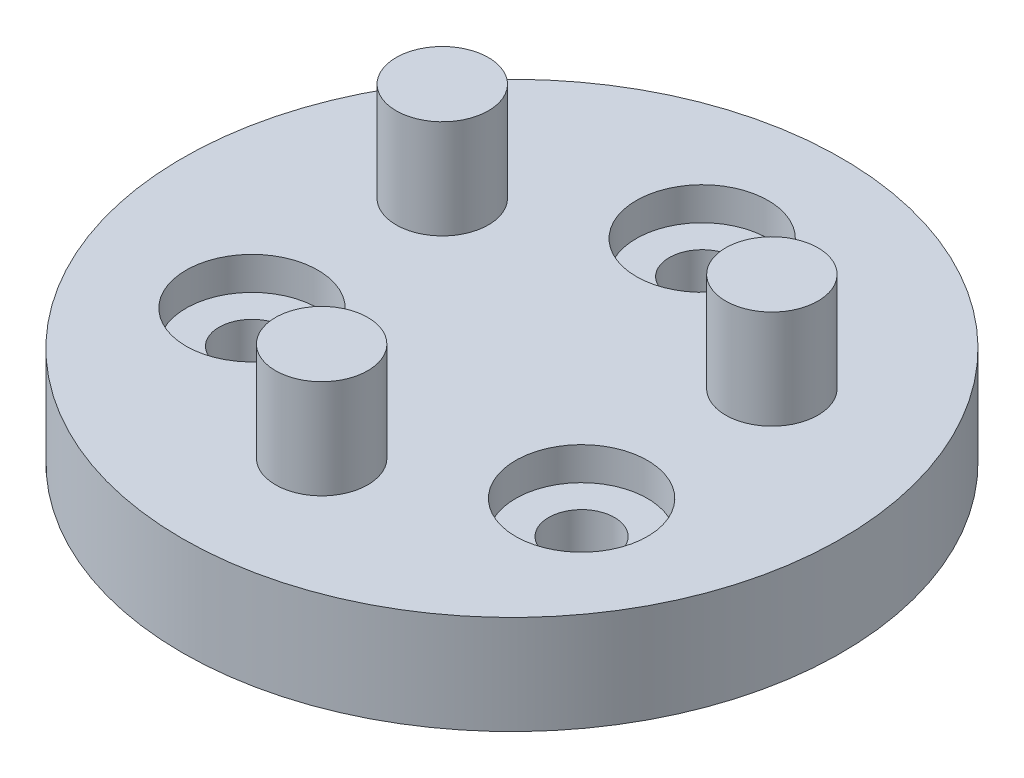
SolidWorks part; units mm, degrees
ref_plane "Front Plane" through (0, 0, 0) normal (0, 0, 1) x (1, 0, 0)
ref_plane "Top Plane" through (0, 0, 0) normal (0, 1, 0) x (1, 0, 0)
ref_plane "Right Plane" through (0, 0, 0) normal (1, 0, 0) x (0, 0, -1)
sketch "Sketch1" plane through (0, 0, 0) normal (0, 1, 0) x (1, 0, 0)
  line L1 (0, 5.7735) -> (-5, -2.8868) construction
  line L2 (-5, -2.8868) -> (5, -2.8868) construction
  line L3 (5, -2.8868) -> (0, 5.7735) construction
  circle A0 centre (0, 0) radius 10
  circle A1 centre (0, 0) radius 2.8868 construction
  circle A2 centre (0, 5.7735) radius 1
  circle A3 centre (-5, -2.8868) radius 1
  circle A4 centre (5, -2.8868) radius 1
  dimension "D1" = 10
extrude "Boss-Extrude1" add sketch "Sketch1" along normal blind 3
sketch "Sketch2" plane through (0, 3, 0) normal (0, 1, 0) x (1, 0, 0)
  circle A0 centre (0, 5.7735) radius 2
  circle A1 centre (-5, -2.8868) radius 2
  circle A2 centre (5, -2.8868) radius 2
extrude "Cut-Extrude1" cut sketch "Sketch2" against normal blind 1
sketch "Sketch4" plane through (0, 3, 0) normal (0, 1, 0) x (1, 0, 0)
  line L0 (-5, -2.8868) -> (0, 5.7735) construction
  line L2 (-5, 2.8868) -> (0, -5.7735) construction
  line L3 (0, -5.7735) -> (5, 2.8868) construction
  line L4 (5, 2.8868) -> (-5, 2.8868) construction
  circle A1 centre (0, 0) radius 2.8868 construction
  circle A2 centre (-5, 2.8868) radius 1.4
  circle A3 centre (5, 2.8868) radius 1.4
  circle A4 centre (0, -5.7735) radius 1.4
extrude "Boss-Extrude2" add sketch "Sketch4" along normal blind 3
